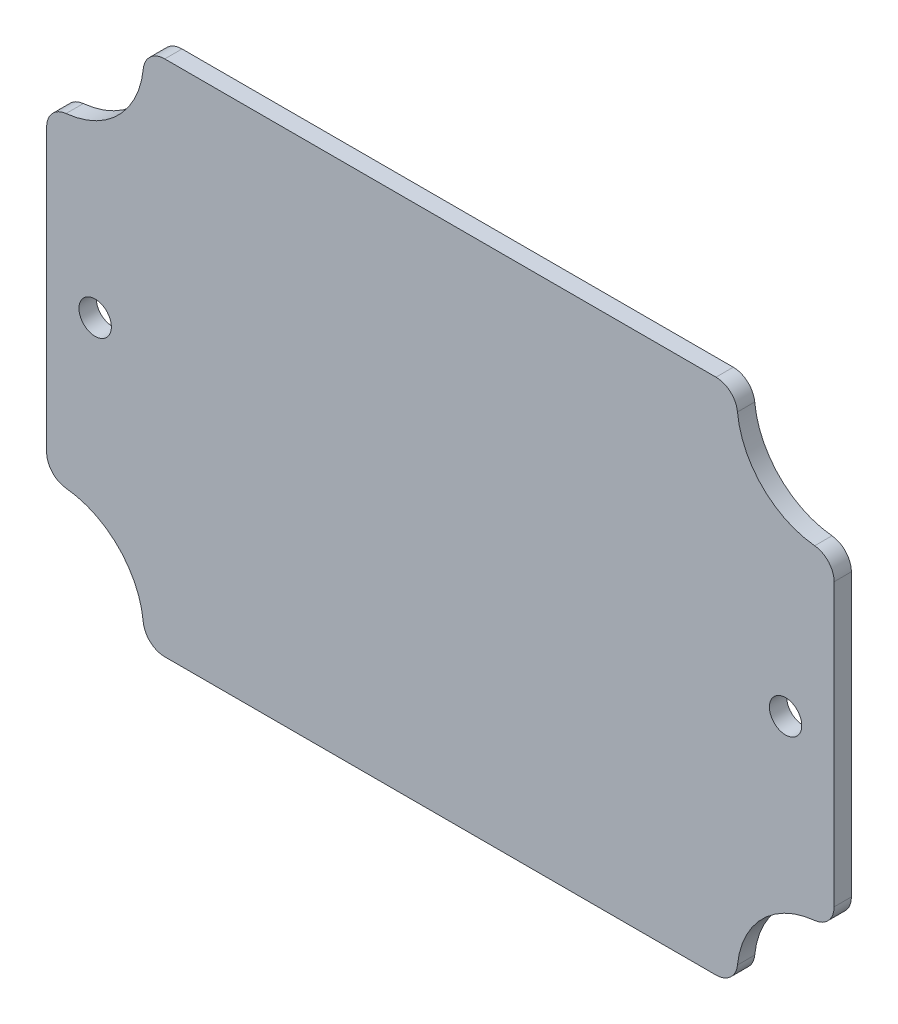
SolidWorks part; units mm, degrees
ref_plane "Front Plane" through (0, 0, 0) normal (0, 0, 1) x (1, 0, 0)
ref_plane "Top Plane" through (0, 0, 0) normal (0, 1, 0) x (1, 0, 0)
ref_plane "Right Plane" through (0, 0, 0) normal (1, 0, 0) x (0, 0, -1)
sketch "Sketch1" plane through (0, 0, 0) normal (0, 0, 1) x (1, 0, 0)
  line L0 (0, 24) -> (0, -24) construction
  line L1 (-36.5, 24) -> (36.5, 24)
  line L2 (-36.5, 24) -> (-36.5, -24)
  line L3 (-36.5, -24) -> (36.5, -24)
  line L4 (36.5, 24) -> (36.5, -24)
  dimension "D1" = 48
  dimension "D2" = 73
extrude "Boss-Extrude1" add sketch "Sketch1" along normal blind 1.6
sketch "Sketch2" plane through (0, 0, 1.6) normal (0, 0, 1) x (1, 0, 0)
  line L0 (-27.5, 23) -> (-27.5, 24)
  line L1 (36.5, 24) -> (-36.5, 24) construction
  line L2 (-27.5, 24) -> (-36.5, 24)
  line L3 (-36.5, 24) -> (-36.5, 15)
  line L4 (-36.5, 24) -> (-36.5, -24) construction
  line L5 (-36.5, 15) -> (-35.5, 15)
  line L6 (36.5, 24) -> (27.5, 24) construction
  line L7 (-36.5, -24) -> (-36.5, -15) construction
  arc A0 (-35.5, 15) -> (-27.5, 23) centre (-35.5, 23) ccw
  dimension "D3" = 8
  dimension "D1" = 30
  dimension "D2" = 55
extrude "Cut-Extrude1" cut sketch "Sketch2" against normal through all
mirror "Mirror1" about plane through (0, 0, 0) normal (1, 0, 0) of "Cut-Extrude1" second plane through (0, 0, 0) second plane normal (0, 1, 0)
fillet "Fillet1" radius 2 32 edges at (-27.5, 23, 0.8) (-36, 15, 0) (-35.5, 15, 0.8) (-36.5, 15, 0.8) (-27.5, 23.5, 0) (-27.5, 24, 0.8) (-27.5, 23.5, 1.6) (-36, 15, 1.6) (-35.5, -15, 0.8) (-27.5, -23.5, 1.6) (-27.5, -23, 0.8) (-27.5, -24, 0.8) (-36, -15, 1.6) (-36.5, -15, 0.8) (-27.5, -23.5, 0) (-36, -15, 0) (35.5, 15, 0.8) (27.5, 23.5, 1.6) (27.5, 23, 0.8) (27.5, 24, 0.8) (36, 15, 1.6) (36.5, 15, 0.8) (27.5, 23.5, 0) (36, 15, 0) (27.5, -23, 0.8) (36, -15, 0) (35.5, -15, 0.8) (36.5, -15, 0.8) (27.5, -23.5, 0) (27.5, -24, 0.8) (27.5, -23.5, 1.6) (36, -15, 1.6)
sketch "Sketch3" plane through (0, 0, 1.6) normal (0, 0, 1) x (1, 0, 0)
  line L0 (-32, 0) -> (32, 0) construction
  circle A0 centre (-32, 0) radius 1.5
  circle A1 centre (32, 0) radius 1.5
  dimension "D1" = 3
  dimension "D2" = 64
extrude "Cut-Extrude2" cut sketch "Sketch3" against normal through all
